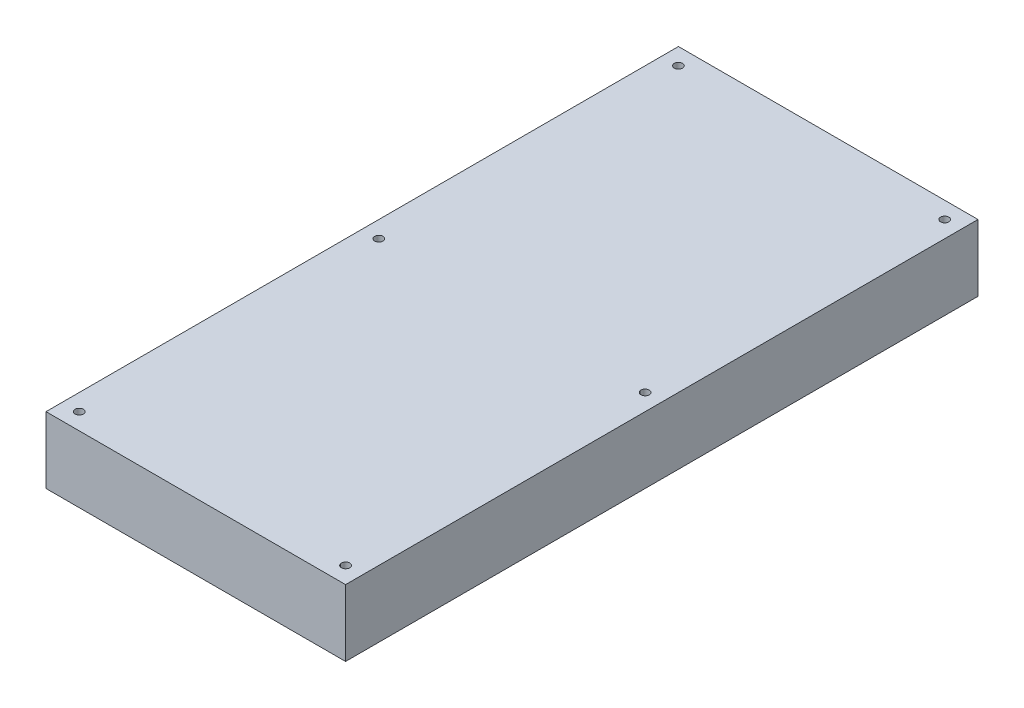
SolidWorks part; units mm, degrees
ref_plane "Front Plane" through (0, 0, 0) normal (0, 0, 1) x (1, 0, 0)
ref_plane "Top Plane" through (0, 0, 0) normal (0, 1, 0) x (1, 0, 0)
ref_plane "Right Plane" through (0, 0, 0) normal (1, 0, 0) x (0, 0, -1)
sketch "Sketch1" plane through (0, 0, 0) normal (0, 1, 0) x (1, 0, 0)
  line L1 (45, 95) -> (-45, 95)
  line L2 (45, 95) -> (45, -95)
  line L3 (45, -95) -> (-45, -95)
  line L4 (-45, 95) -> (-45, -95)
  line L5 (45, 95) -> (-45, -95) construction
  line L6 (45, -95) -> (-45, 95) construction
  point P0 (0, 0)
  dimension "D1" = 190
  dimension "D2" = 90
extrude "Boss-Extrude1" add sketch "Sketch1" along normal mid plane 20
sketch "Sketch2" plane through (0, 10, 0) normal (0, 1, 0) x (1, 0, 0)
  line L0 (45, 95) -> (-45, 95) construction
  line L1 (-45, 95) -> (-45, -95) construction
  circle A0 centre (-40, -90) radius 1.25
  circle A1 centre (40, -90) radius 1.25
  circle A2 centre (-40, 0) radius 1.25
  circle A3 centre (-40, 90) radius 1.25
  circle A4 centre (40, 90) radius 1.25
  circle A5 centre (40, 0) radius 1.25
  dimension "D1" = 2.5
  dimension "D2" = 2.5
  dimension "D3" = 2.5
  dimension "D4" = 2.5
  dimension "D5" = 2.5
  dimension "D6" = 2.5
  dimension "D7" = 90
  dimension "D8" = 90
  dimension "D9" = 5
  dimension "D10" = 80
  dimension "D11" = 5
extrude "Cut-Extrude2" cut sketch "Sketch2" against normal through all
ref_axis "Axis1" through (-40, -10, -90) along (0, 1, 0)
ref_axis "Axis2" through (40, -10, -90) along (0, 1, 0)
ref_axis "Axis3" through (-40, -10, 0) along (0, 1, 0)
ref_axis "Axis4" through (40, -10, 0) along (0, 1, 0)
ref_axis "Axis5" through (-40, -10, 90) along (0, 1, 0)
ref_axis "Axis6" through (40, -10, 90) along (0, 1, 0)
ref_point "Point1"
ref_point "Point2"
ref_point "Point3"
ref_point "Point4"
ref_point "Point5"
ref_point "Point6"
